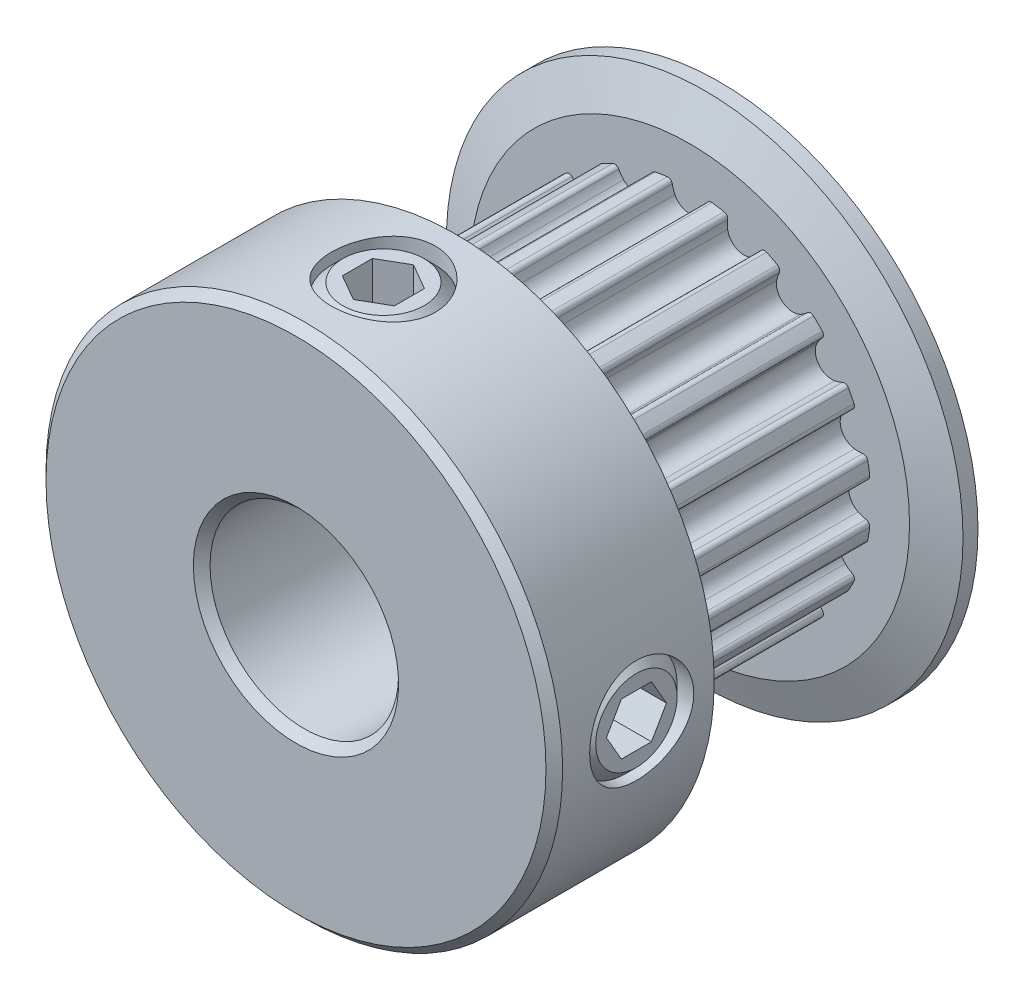
SolidWorks part; units mm, degrees
ref_plane "Front Plane" through (0, 0, 0) normal (0, 0, 1) x (1, 0, 0)
ref_plane "Top Plane" through (0, 0, 0) normal (0, 1, 0) x (1, 0, 0)
ref_plane "Right Plane" through (0, 0, 0) normal (1, 0, 0) x (0, 0, -1)
sketch "Sketch1" plane through (0, 0, 0) normal (0, 0, 1) x (1, 0, 0)
  line L1 (-1.7499, 5.3585) -> (1.7499, 5.3585) construction
  line L4 (0, 0) -> (0, 5.3585) construction
  line L5 (0, 5.3585) -> (0, 11.2107) construction
  line L6 (0, 6.3625) -> (1.9751, 6.0482) construction
  line L7 (1.9751, 6.0482) -> (2.6648, 5.8229) construction
  line L8 (1.9751, 6.0482) -> (1.7499, 5.3585) construction
  line L9 (-1.9751, 6.0482) -> (-1.7499, 5.3585) construction
  line L10 (-1.8963, 5.8067) -> (-2.841, 8.6995)
  line L11 (-2.841, 8.6995) -> (2.841, 8.6995)
  line L12 (2.841, 8.6995) -> (1.8963, 5.8067)
  circle A0 centre (0, 0) radius 6.3625 construction
  circle A1 centre (0, 0) radius 8.6995 construction
  circle A2 centre (0, 0) radius 6.1085 construction
  arc A3 (-0.4989, 5.6703) -> (0.4989, 5.6703) centre (0, 5.9135) ccw
  arc A4 (-0.4989, 5.6703) -> (-0.5855, 5.9387) centre (0.4, 6.1085) cw
  arc A5 (-1.8963, 5.8067) -> (-0.7518, 6.0621) centre (0, 0) cw
  arc A6 (-0.5855, 5.9387) -> (-0.7518, 6.0621) centre (-0.7333, 5.9132) ccw
  arc A7 (1.8963, 5.8067) -> (0.7518, 6.0621) centre (0, 0) ccw
  arc A8 (0.5855, 5.9387) -> (0.7518, 6.0621) centre (0.7333, 5.9132) cw
  arc A9 (0.4989, 5.6703) -> (0.5855, 5.9387) centre (-0.4, 6.1085) ccw
  point P6 (0, 20.9083)
  point P11 (0, 6.3625)
  point P13 (0, 8.6995)
  point P14 (0, 6.1085)
  dimension "D1" = 9.6976
  dimension "D2" = 4.8482
sketch "Sketch2" plane through (0, 0, 0) normal (1, 0, 0) x (0, 0, -1)
  line L0 (-7.135, 3.175) -> (7.135, 3.175)
  line L1 (-7.135, 3.175) -> (-7.135, 8.6995)
  line L2 (-1.75, 8.6995) -> (-7.135, 8.6995)
  line L3 (-2.255, 3.175) -> (-2.255, 8.6995) construction
  line L4 (-2.255, 8.6995) -> (-1.245, 8.6995) construction
  line L5 (-1.245, 8.6995) -> (-1.245, 6.1085) construction
  line L6 (-1.245, 6.1085) -> (6.125, 6.1085)
  line L7 (6.125, 6.1085) -> (6.125, 8.6995) construction
  line L8 (6.125, 8.6995) -> (7.135, 8.6995) construction
  line L9 (7.135, 8.6995) -> (7.135, 3.175)
  line L10 (-7.135, 0) -> (7.135, 0) construction
  line L11 (6.63, 8.6995) -> (6.125, 7.404)
  line L12 (-1.245, 7.404) -> (-1.75, 8.6995)
  line L14 (-1.245, 7.404) -> (-1.245, 6.1085)
  line L15 (6.125, 6.1085) -> (6.125, 7.404)
  line L16 (6.63, 8.6995) -> (7.135, 8.6995)
  arc A0 (-1.245, 7.404) -> (-1.75, 8.6995) centre (-3.1592, 7.404) ccw construction
  arc A1 (6.125, 7.404) -> (6.63, 8.6995) centre (8.0392, 7.404) cw construction
  point P12 (-1.245, 7.404)
  point P14 (-1.75, 8.6995)
  point P20 (6.125, 7.404)
  point P21 (6.63, 8.6995)
  point P25 (6.125, 0)
  point P26 (-1.245, 0)
  dimension "OA" = 14.27
  dimension "Bore" = 6.35
  dimension "Outside Width" = 8.38
  dimension "Inside Width" = 7.37
revolve "Revolve1" add sketch "Sketch2" angle 360 mid plane about L10
sketch "Sketch3" plane through (0, 0, 0) normal (0, 0, 1) x (1, 0, 0)
  line L6 (2.841, 8.6995) -> (-2.841, 8.6995)
  line L7 (1.8963, 5.8067) -> (2.841, 8.6995)
  line L8 (-2.841, 8.6995) -> (-1.8963, 5.8067)
  line L9 (2.841, 8.6995) -> (-2.841, 8.6995)
  line L10 (1.8963, 5.8067) -> (2.841, 8.6995)
  line L11 (-2.841, 8.6995) -> (-1.8963, 5.8067)
  arc A8 (1.8963, 5.8067) -> (0.7518, 6.0621) centre (0, 0) ccw
  arc A9 (0.7518, 6.0621) -> (0.5855, 5.9387) centre (0.7333, 5.9132) ccw
  arc A10 (0.4989, 5.6703) -> (0.5855, 5.9387) centre (-0.4, 6.1085) ccw
  arc A11 (-0.4989, 5.6703) -> (0.4989, 5.6703) centre (0, 5.9135) ccw
  arc A12 (-0.5855, 5.9387) -> (-0.4989, 5.6703) centre (0.4, 6.1085) ccw
  arc A13 (-0.5855, 5.9387) -> (-0.7518, 6.0621) centre (-0.7333, 5.9132) ccw
  arc A14 (-0.7518, 6.0621) -> (-1.8963, 5.8067) centre (0, 0) ccw
  arc A15 (1.8963, 5.8067) -> (0.7518, 6.0621) centre (0, 0) ccw
  arc A16 (0.7518, 6.0621) -> (0.5855, 5.9387) centre (0.7333, 5.9132) ccw
  arc A17 (0.4989, 5.6703) -> (0.5855, 5.9387) centre (-0.4, 6.1085) ccw
  arc A18 (-0.4989, 5.6703) -> (0.4989, 5.6703) centre (0, 5.9135) ccw
  arc A19 (-0.5855, 5.9387) -> (-0.4989, 5.6703) centre (0.4, 6.1085) ccw
  arc A20 (-0.5855, 5.9387) -> (-0.7518, 6.0621) centre (-0.7333, 5.9132) ccw
  arc A21 (-0.7518, 6.0621) -> (-1.8963, 5.8067) centre (0, 0) ccw
  dimension "D1" = 0
extrude "Cut-Extrude1" cut sketch "Sketch3" against normal up to vertex (6.125 mm away) from vertex up to point (0, 6.1085, -6.125) starting at point (0, 6.1085, 1.245)
pattern_circular "CirPattern1" count 20 over 360 about axis through (0, 0, 7.135) along (0, 0, 1) of "Cut-Extrude1"
sketch "Sketch4" plane through (0, 0, 0) normal (1, 0, 0) x (0, -1, 0)
  line L0 (0, -1.245) -> (0, -7.135) construction
  line L1 (-3.175, -7.135) -> (3.175, -7.135) construction
  line L2 (7.404, -1.245) -> (-7.404, -1.245) construction
  circle A0 centre (0, -4.19) radius 1.7526
extrude "Cut-Extrude2" cut sketch "Sketch4" along normal through all
ref_plane "Plane1" through (0, 0, 4.19) normal (0, 0, 1) x (1, 0, 0)
sketch "Sketch5" plane through (0, 0, 4.19) normal (0, 0, 1) x (1, 0, 0)
  line L0 (0, 0) -> (0, 8.6995) construction
  line L1 (3.175, -1.3716) -> (3.175, 0)
  line L2 (3.556, -1.7526) -> (8.1401, -1.7526)
  line L3 (3.175, 0) -> (8.6995, 0) construction
  line L4 (3.175, 0) -> (8.5211, 0)
  line L5 (8.5211, 0) -> (8.5211, -1.3716)
  line L6 (3.556, -1.7526) -> (3.175, -1.3716)
  line L7 (8.5211, -1.3716) -> (8.1401, -1.7526)
  circle A0 centre (0, 0) radius 8.6995 construction
  circle A1 centre (0, 0) radius 3.175 construction
  point P2 (3.175, -1.7526)
  point P11 (8.5211, -1.7526)
revolve "Revolve2" add sketch "Sketch5" angle 360 mid plane about L4
sketch "Sketch6" plane through (8.5211, 5.3841, 0) normal (-1, 0, 0) x (0, -1, 0)
  line L1 (5.3841, 5.2019) -> (4.5078, 4.6959)
  line L2 (4.5078, 4.6959) -> (4.5078, 3.6841)
  line L3 (4.5078, 3.6841) -> (5.3841, 3.1781)
  line L4 (5.3841, 3.1781) -> (6.2604, 3.6841)
  line L5 (6.2604, 3.6841) -> (6.2604, 4.6959)
  line L6 (6.2604, 4.6959) -> (5.3841, 5.2019)
  circle A0 centre (5.3841, 4.19) radius 0.8763 construction
  dimension "D1" = 1.7526
extrude "Cut-Extrude3" cut sketch "Sketch6" along normal blind 1.3144
pattern_circular "CirPattern3" count 2 over 90 about axis through (0, 0, 7.135) along (0, 0, 1) of "Cut-Extrude2", "Revolve2", "Cut-Extrude3"
chamfer "Chamfer1" distance 0.2807 angle 45 2 edges at (3.175, 0, 7.135) (8.6995, 0, 7.135)
ref_axis "Center Axis 1" through (0, 0, -7.135) along (0, 0, 1)
ref_plane "Contact Plane 1" through (0, 0, 7.135) normal (0, 0, 1) x (1, 0, 0)
ref_plane "Contact Plane 2" through (0, 0, -7.135) normal (0, 0, -1) x (-1, 0, 0)
equation "\"D2@Sketch1\"= \"D1@Sketch1\" / 2"
equation "\"D1@Sketch6\" = \"Set Screw@Sketch4\" / 2"
equation "\"D1@Cut-Extrude3\" = \"D1@Sketch6\"*.75"
